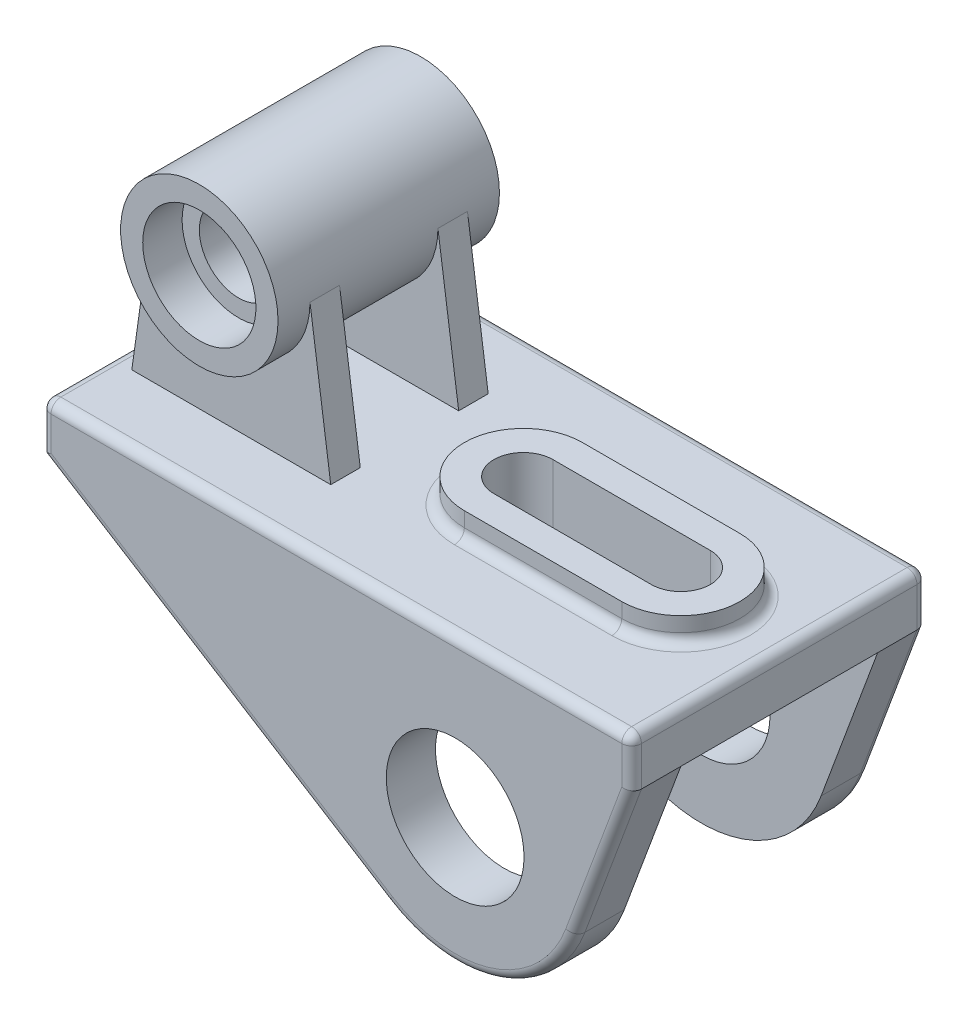
SolidWorks part; units mm, degrees
material "티타늄"
ref_plane "정면" through (0, 0, 0) normal (0, 0, 1) x (1, 0, 0)
ref_plane "윗면" through (0, 0, 0) normal (0, 1, 0) x (1, 0, 0)
ref_plane "우측면" through (0, 0, 0) normal (1, 0, 0) x (0, 0, -1)
sketch "Sketch1" plane through (0, 0, 0) normal (0, 1, 0) x (1, 0, 0)
  line L1 (0, 0) -> (120, 0)
  line L2 (0, 0) -> (0, 60)
  line L3 (0, 60) -> (120, 60)
  line L4 (120, 0) -> (120, 60)
  dimension "D1" = 60
  dimension "D2" = 120
extrude "Boss-Extrude1" add sketch "Sketch1" along normal blind 10
sketch "Sketch2" plane through (0, 0, 0) normal (0, 0, 1) x (1, 0, 0)
  line L0 (0, 10) -> (0, 0)
  line L1 (0, 10) -> (120, 10) construction
  line L2 (0, 0) -> (70.3573, -43.9641)
  line L3 (108.511, -30.9604) -> (120, 0)
  line L4 (120, 0) -> (120, 10)
  line L5 (120, 10) -> (0, 10)
  arc A0 (70.3573, -43.9641) -> (108.511, -30.9604) centre (84.1352, -21.9149) ccw
  dimension "D1" = 26
  dimension "D2" = 32
ref_plane "Plane1" through (0, 0, -30) normal (0, 0, 1) x (1, 0, 0)
extrude "Boss-Extrude2" add sketch "Sketch2" against normal blind 10 contours L3 L4 L5 L0 L2 A0
mirror "Mirror1" about plane through (0, 0, -30) normal (0, 0, 1) of "Boss-Extrude2"
hole_wizard "Ø25.0 (28) Diameter Hole1" positions "3DSketch1" profile "Sketch4" hole size "Ø25.0" standard "Ansi Metric" end condition through all
sketch3d "3DSketch1"
  line L0 (84.1352, -21.9149, -10) -> (84.1352, -21.9149, 0) construction
  point P0 (84.1352, -21.9149, 0)
sketch "Sketch4" plane through (84.1352, -21.9149, 0) normal (1, 0, 0) x (0, -1, 0)
  line L0 (0, 0) -> (0, 60)
  line L1 (0, 60) -> (14, 60)
  line L2 (14, 60) -> (14, 0)
  line L5 (14, 0) -> (0, 0)
  line L11 (0, -6.35) -> (0, 107.95) construction
  dimension "관통 구멍 지름" = 28
  dimension "관통 구멍 깊이" = 60
sketch "Sketch5" plane through (0, 10, 0) normal (0, 1, 0) x (1, 0, 0)
  line L0 (100, 30) -> (68, 30) construction
  line L1 (-31.8532, 30) -> (31.8532, 30) construction
  line L2 (100, 18) -> (68, 18)
  line L3 (100, 42) -> (68, 42)
  line L4 (100, 30) -> (68, 30) construction
  line L5 (100, 24) -> (68, 24)
  line L6 (100, 36) -> (68, 36)
  line L7 (120, 0) -> (120, 60) construction
  arc A0 (100, 18) -> (100, 42) centre (100, 30) ccw
  arc A1 (68, 42) -> (68, 18) centre (68, 30) ccw
  arc A2 (100, 24) -> (100, 36) centre (100, 30) ccw
  arc A3 (68, 36) -> (68, 24) centre (68, 30) ccw
  point P4 (84, 30)
  point P11 (84, 30)
  dimension "D1" = 12
  dimension "D2" = 6
  dimension "D3" = 20
  dimension "D4" = 32
extrude "Boss-Extrude3" add sketch "Sketch5" along normal blind 5
extrude "Cut-Extrude1" cut sketch "Sketch5<2>" against normal through all contours L6 A3 L5 A2 region at (84, 10, -30)
sketch "Sketch5<2>" plane through (0, 10, 0) normal (0, 1, 0) x (1, 0, 0) same geometry as "Sketch5"
sketch "Sketch7" plane through (0, 0, -30) normal (0, 0, 1) x (1, 0, 0)
  line L0 (8.6358, 40) -> (4.4196, 10)
  line L1 (0, 10) -> (120, 10) construction
  line L2 (24.6358, 63.3898) -> (24.6358, 7.2501) construction
  line L3 (40.6358, 40) -> (44.852, 10)
  line L4 (4.4196, 10) -> (44.852, 10)
  circle A0 centre (24.6358, 40) radius 16
  circle A1 centre (24.6358, 40) radius 11.5
  circle A2 centre (24.6358, 40) radius 8
  dimension "D1" = 32
  dimension "D3" = 23
  dimension "D4" = 16
  dimension "D2" = 16
  dimension "D5" = 30
extrude "Boss-Extrude4" add sketch "Sketch7" along normal mid plane 45 separate body contours L2 A0 | A0 L2 region at (24.6358, 55.5475, -30)
extrude "Boss-Extrude5" add sketch "Sketch7<3>" along normal mid plane 32 contours A0 L2 L4 L3 | L2 A0 L0 L4 region at (14.1868, 19.2521, -30) region at (35.0848, 19.2521, -30)
sketch "Sketch7<3>" plane through (0, 0, -30) normal (0, 0, 1) x (1, 0, 0) same geometry as "Sketch7"
extrude "Cut-Extrude2" cut sketch "Sketch7<5>" against normal mid plane 20 contours L2 A0 L0 L4 | A0 L2 L4 L3 region at (14.1868, 19.2521, -30) region at (35.0848, 19.2521, -30)
sketch "Sketch7<5>" plane through (0, 0, -30) normal (0, 0, 1) x (1, 0, 0) same geometry as "Sketch7"
extrude "Boss-Extrude6" add sketch "Sketch7<7>" along normal blind 14.5 and the other way blind 22.5 contours L2 A1 A2 | A1 L2 A2 region at (32.5857, 47.9499, -30) region at (24.3786, 49.75, -30)
sketch "Sketch7<7>" plane through (0, 0, -30) normal (0, 0, 1) x (1, 0, 0) same geometry as "Sketch7"
fillet "Fillet1" radius 2 18 edges at (114.2555, -15.4802, -60) (92.5229, -46.5248, -60) (114.2555, -15.4802, 0) (92.5229, -46.5248, 0) (84, 10, -18) (56, 10, -30) (84, 10, -42) (120, 5, -60) (120, 5, 0) (0, 5, -60) (35.1787, -21.9821, -60) (0, 5, 0) (35.1787, -21.9821, 0) (60, 10, -60) (0, 10, -30) (120, 10, -30) (60, 10, 0) (112, 10, -30)
